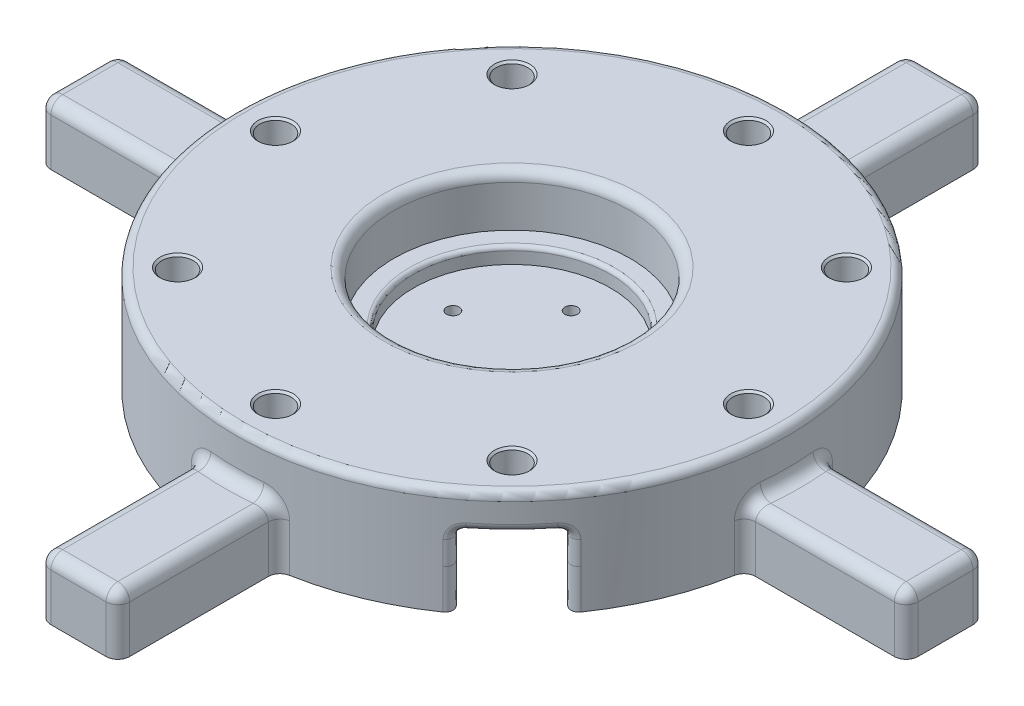
SolidWorks part; units mm, degrees
ref_plane "前视基准面" through (0, 0, 0) normal (0, 0, 1) x (1, 0, 0)
ref_plane "上视基准面" through (0, 0, 0) normal (0, 1, 0) x (1, 0, 0)
ref_plane "右视基准面" through (0, 0, 0) normal (1, 0, 0) x (0, 0, -1)
other "Configuration Table"
sketch "草图1" plane through (0, 0, 0) normal (1, 0, 0) x (0, 0, -1)
  line L0 (0, 0) -> (25, 0)
  line L1 (25, 0) -> (25, 4)
  line L2 (25, 4) -> (30, 4)
  line L3 (30, 4) -> (30, 17)
  line L5 (0, 0) -> (0, -5)
  line L6 (0, -5) -> (25, -5)
  line L7 (25, -5) -> (25, -10)
  line L8 (25, -10) -> (70, -10)
  line L9 (70, -10) -> (70, 17)
  line L11 (30, 17) -> (70, 17)
revolve "旋转1" add sketch "草图1" angle 360 about L5
sketch "草图2" plane through (0, 0, 0) normal (0, 1, 0) x (1, 0, 0)
  circle A0 centre (15, 0) radius 1.6
  circle A1 centre (0, -15) radius 1.6
  circle A2 centre (-15, 0) radius 1.6
  circle A3 centre (0, 15) radius 1.6
  point P13 (0, 0)
  dimension "D1" = 4
extrude "切除-拉伸1" cut sketch "草图2" against normal blind 10 contours A0 | A1 | A2 | A3
sketch "草图3" plane through (0, -10, 0) normal (0, -1, 0) x (1, 0, 0)
  line L20 (-110, -10) -> (-69.282, -10)
  line L21 (10, 110) -> (10, 69.282)
  line L22 (-110, -10) -> (-110, 10)
  line L23 (-110, 10) -> (-69.282, 10)
  line L24 (-10, 110) -> (10, 110)
  line L25 (-10, 110) -> (-10, 69.282)
  line L26 (110, -10) -> (69.282, -10)
  line L27 (110, 10) -> (110, -10)
  line L28 (110, 10) -> (69.282, 10)
  line L29 (-10, -110) -> (-10, -69.282)
  line L30 (10, -110) -> (-10, -110)
  line L31 (10, -110) -> (10, -69.282)
  arc A22 (-69.282, 10) -> (-69.282, -10) centre (0, 0) ccw
  arc A23 (10, 69.282) -> (-10, 69.282) centre (0, 0) ccw
  arc A24 (69.282, -10) -> (69.282, 10) centre (0, 0) ccw
  arc A25 (-10, -69.282) -> (10, -69.282) centre (0, 0) ccw
  point P19 (0, 0)
  point P54 (0, 0)
  dimension "D1" = 4
extrude "凸台-拉伸1" add sketch "草图3" against normal blind 15
sketch "草图4" plane through (0, 0, 0) normal (0, 1, 0) x (1, 0, 0)
  line L2 (0, 0) -> (14.0646, 14.0646)
ref_plane "基准面1" through (0, 0, 0) normal (0.7071, 0, 0.7071) x (0.7071, 0, -0.7071)
sketch "草图5" plane through (0, 0, 0) normal (0.7071, 0, 0.7071) x (0.7071, 0, -0.7071)
  line L0 (0, 0) -> (10, 0)
  line L1 (10, 0) -> (10, 5)
  line L3 (-10, 5) -> (-10, 0)
  line L4 (-10, 0) -> (0, 0)
  line L5 (10, 5) -> (10, 8)
  line L6 (10, 8) -> (-10, 8)
  line L7 (-10, 8) -> (-10, 5)
extrude "切除-拉伸2" cut sketch "草图5" along normal blind 97
fillet "圆角6" radius 2 2 edges at (41.566, 8, 27.4238) (27.4238, 8, 41.566)
fillet "圆角7" radius 0.5 4 edges at (15, -5, 1.6) (0, -5, 16.6) (-15, -5, 1.6) (0, -5, -13.4)
fillet "圆角9" radius 2 5 edges at (56.0609, 3, 41.9187) (55.6082, 7.556, 42.5174) (49.4975, 8, 49.4975) (42.2665, 7.2403, 55.7991) (41.9187, 3, 56.0609)
fillet "圆角10" radius 3 32 edges at (-10, -2.5, 69.282) (0, 5, 70) (-10, -2.5, 110) (10, -2.5, 110) (0, 5, 110) (-10, 5, 89.641) (10, 5, 89.641) (10, -2.5, 69.282) (-69.282, -2.5, 10) (-69.282, -2.5, -10) (-70, 5, 0) (-89.641, 5, 10) (-110, -2.5, 10) (-110, 5, 0) (-89.641, 5, -10) (-110, -2.5, -10) (10, -2.5, -110) (-10, -2.5, -110) (-10, -2.5, -69.282) (-10, 5, -89.641) (0, 5, -70) (10, -2.5, -69.282) (10, 5, -89.641) (0, 5, -110) (69.282, -2.5, 10) (110, -2.5, 10) (110, -2.5, -10) (69.282, -2.5, -10) (70, 5, 0) (89.641, 5, 10) (110, 5, 0) (89.641, 5, -10)
fillet "圆角11" radius 2.5 1 edges at (0, 17, 30)
fillet "圆角12" radius 1 1 edges at (-17.6777, 4, -17.6777)
sketch "草图6" plane through (0, 0, 0) normal (0, 1, 0) x (1, 0, 0)
  line L0 (23.2729, -9.1308) -> (56.0609, -41.9187)
  line L2 (41.9187, -56.0609) -> (9.1308, -23.2729)
  arc A0 (9.1308, -23.2729) -> (23.2729, -9.1308) centre (0, 0) ccw
  arc A1 (41.9187, -56.0609) -> (56.0609, -41.9187) centre (0, 0) ccw
extrude "切除-拉伸4" cut sketch "草图6" against normal blind 10
fillet "圆角13" radius 2 2 edges at (41.9187, -5, 56.0609) (56.0609, -5, 41.9187)
sketch "草图7" plane through (0, 17, 0) normal (0, 1, 0) x (1, 0, 0)
  circle A1 centre (0, 60) radius 4
  circle A2 centre (42.4264, 42.4264) radius 4
  circle A3 centre (60, 0) radius 4
  circle A4 centre (42.4264, -42.4264) radius 4
  circle A5 centre (0, -60) radius 4
  circle A6 centre (-42.4264, -42.4264) radius 4
  circle A7 centre (-60, 0) radius 4
  circle A8 centre (-42.4264, 42.4264) radius 4
  point P20 (0, 0)
  dimension "D1" = 8
extrude "切除-拉伸5" cut sketch "草图7" against normal blind 9
fillet "圆角14" radius 2 1 edges at (0, 17, 70)
chamfer "倒角1" distance 0.5 angle 45 8 edges at (-42.4264, 17, -38.4264) (0, 17, -56) (42.4264, 17, -38.4264) (60, 17, 4) (42.4264, 17, 46.4264) (0, 17, 64) (-42.4264, 17, 46.4264) (-60, 17, 4)
fillet "圆角16" radius 2 2 edges at (23.2729, -2.5, 9.1308) (9.1308, -2.5, 23.2729)
